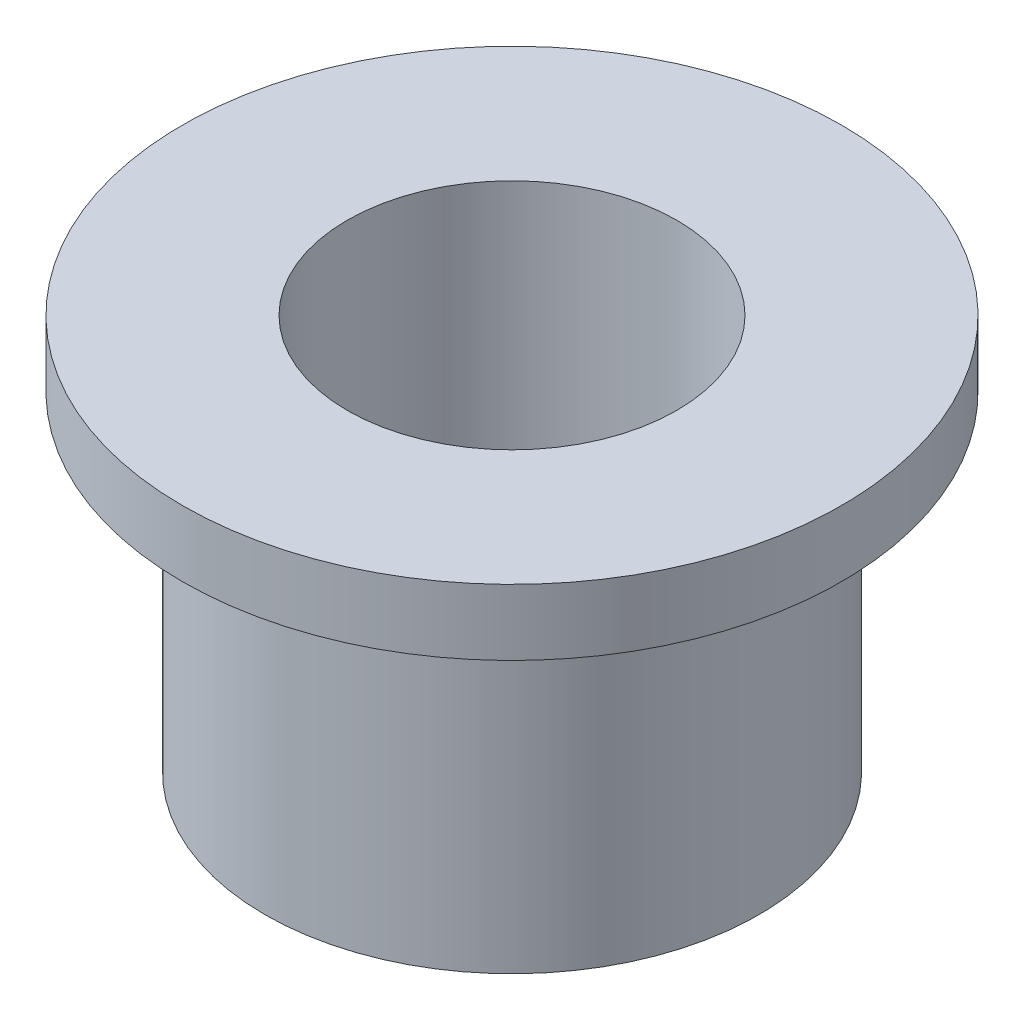
SolidWorks part; units mm, degrees
material "Delrin 2700 NC010, Low Viscosity Acetal Copolymer (SS)"
ref_plane "Front Plane" through (0, 0, 0) normal (0, 0, 1) x (1, 0, 0)
ref_plane "Top Plane" through (0, 0, 0) normal (0, 1, 0) x (1, 0, 0)
ref_plane "Right Plane" through (0, 0, 0) normal (1, 0, 0) x (0, 0, -1)
sketch "Sketch1" plane through (0, 0, 0) normal (0, 0, 1) x (1, 0, 0)
  line L0 (0, 0) -> (0, -10.9677) construction
  line L1 (5, 1.0323) -> (5, -10.9677)
  line L2 (5, -10.9677) -> (7.5, -10.9677)
  line L3 (7.5, -10.9677) -> (7.5, -0.9677)
  line L4 (7.5, -0.9677) -> (10, -0.9677)
  line L5 (10, -0.9677) -> (10, 1.0323)
  line L6 (10, 1.0323) -> (5, 1.0323)
  dimension "D1" = 2
  dimension "D2" = 10
  dimension "D3" = 5
  dimension "D4" = 7.5
  dimension "D5" = 10
revolve "Revolve1" add sketch "Sketch1" angle 360 about L0
